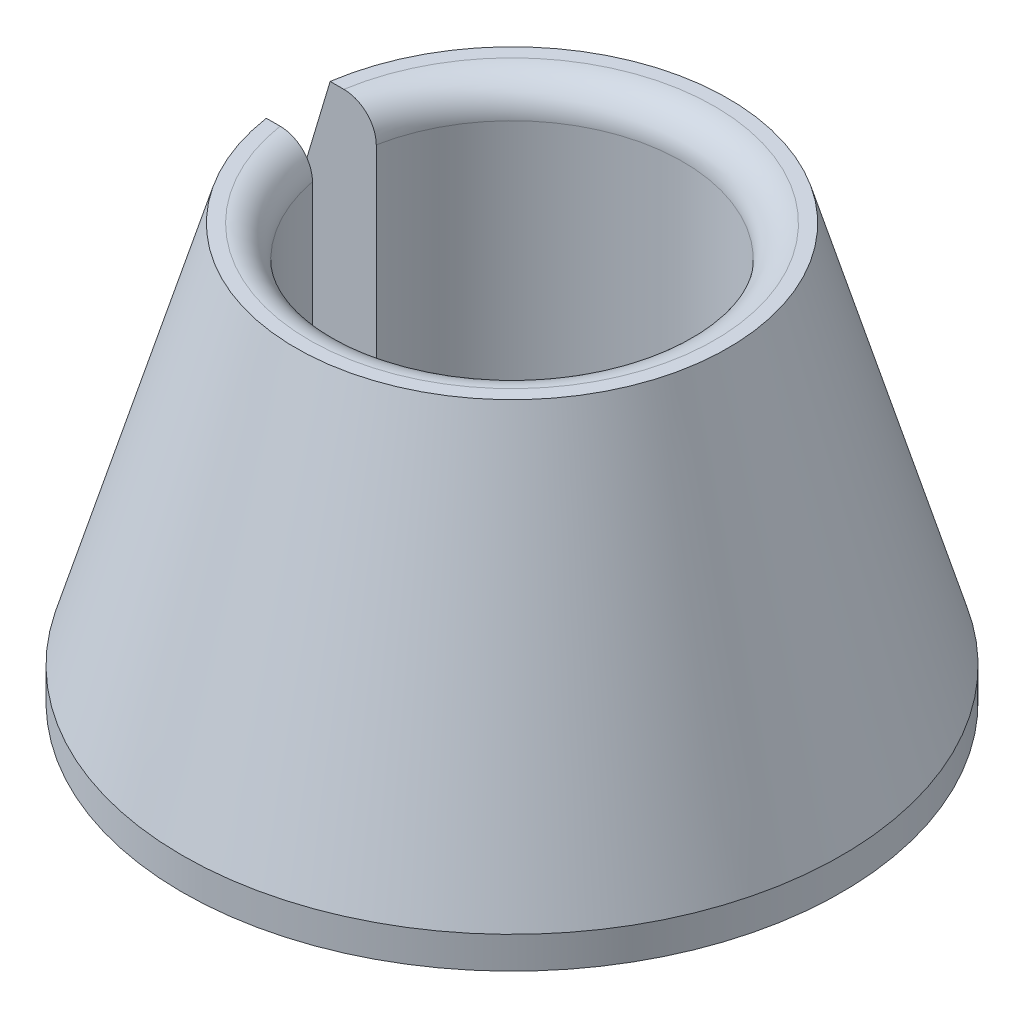
SolidWorks part; units mm, degrees
ref_plane "Front Plane" through (0, 0, 0) normal (0, 0, 1) x (1, 0, 0)
ref_plane "Top Plane" through (0, 0, 0) normal (0, 1, 0) x (1, 0, 0)
ref_plane "Right Plane" through (0, 0, 0) normal (1, 0, 0) x (0, 0, -1)
sketch "Sketch1" plane through (0, 0, 0) normal (0, 1, 0) x (1, 0, 0)
  circle A0 centre (0, 0) radius 5.165
  circle A1 centre (0, 0) radius 2.675
  dimension "D1" = 10.33
  dimension "D2" = 5.35
extrude "Boss-Extrude1" add sketch "Sketch1" along normal blind 6
chamfer "Chamfer1" distance 6 angle 16.5 1 edges at (0, 6, 5.165) first distance on face at (0, 6, 5.165)
sketch "Sketch2" plane through (0, 6, 0) normal (0, 1, 0) x (1, 0, 0)
  line L0 (0, 0) -> (-6.0172, 0) construction
  line L1 (0, 0.5) -> (-6.0172, 0.5)
  line L2 (0, -0.5) -> (-6.0172, -0.5)
  line L3 (-6.0172, 0.5) -> (-6.0172, -0.5)
  line L4 (0, 0.5) -> (0, -0.5)
  dimension "D1" = 0.5
  dimension "D2" = 0.5
extrude "Cut-Extrude1" cut sketch "Sketch2" against normal through all
sketch "Sketch3" plane through (0, 0, 0) normal (0, -1, 0) x (1, 0, 0)
  line L0 (-2.6279, -0.5) -> (-5.1407, -0.5)
  line L1 (-2.6279, -0.5) -> (-5.1407, -0.5) construction
  line L2 (-2.6279, 0.5) -> (-5.1407, 0.5)
  line L3 (-5.1407, 0.5) -> (-2.6279, 0.5) construction
  arc A0 (-5.1407, -0.5) -> (-5.1407, 0.5) centre (0, 0) ccw
  arc A1 (-2.6279, -0.5) -> (-2.6279, 0.5) centre (0, 0) ccw
extrude "Boss-Extrude2" add sketch "Sketch3" along normal blind 0.5
fillet "Fillet1" radius 0.5 2 edges at (2.675, -0.5, 0) (2.675, 6, 0)
